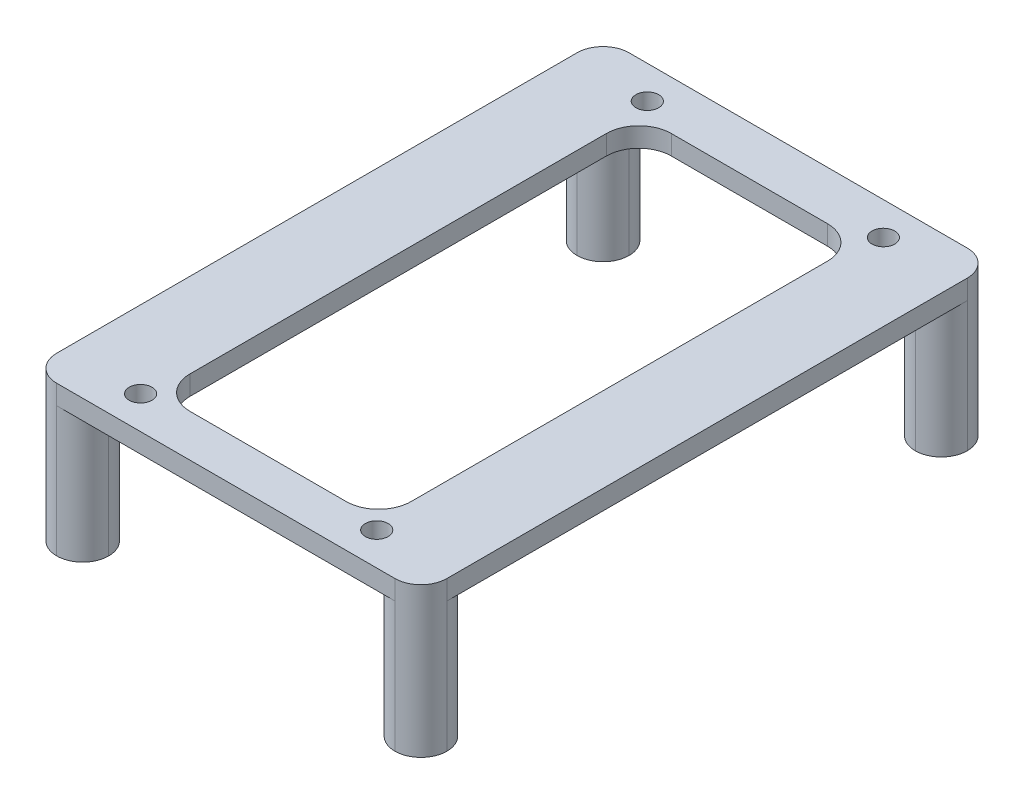
SolidWorks part; units mm, degrees
ref_plane "Front Plane" through (0, 0, 0) normal (0, 0, 1) x (1, 0, 0)
ref_plane "Top Plane" through (0, 0, 0) normal (0, 1, 0) x (1, 0, 0)
ref_plane "Right Plane" through (0, 0, 0) normal (1, 0, 0) x (0, 0, -1)
sketch "Sketch1" plane through (0, 0, 0) normal (0, 1, 0) x (1, 0, 0)
  line L0 (11.85, 82.95) -> (0, 88) construction
  line L1 (0, 0) -> (60, 0)
  line L2 (0, 0) -> (0, 88)
  line L3 (0, 88) -> (60, 88)
  line L4 (60, 0) -> (60, 88)
  line L5 (11.85, 82.95) -> (48.15, 82.95) construction
  line L6 (11.85, 82.95) -> (11.85, 5.05) construction
  line L7 (11.85, 5.05) -> (48.15, 5.05) construction
  line L8 (48.15, 82.95) -> (48.15, 5.05) construction
  line L9 (48.15, 82.95) -> (60, 88) construction
  line L10 (0, 0) -> (11.85, 5.05) construction
  line L11 (48.15, 5.05) -> (60, 0) construction
  line L13 (13, 80.5) -> (47, 80.5)
  line L14 (13, 80.5) -> (13, 6.5)
  line L15 (13, 6.5) -> (47, 6.5)
  line L16 (47, 80.5) -> (47, 6.5)
  circle A0 centre (11.85, 82.95) radius 1.75
  circle A1 centre (48.15, 82.95) radius 1.75
  circle A2 centre (48.15, 5.05) radius 1.75
  circle A3 centre (11.85, 5.05) radius 1.75
  point P18 (11.85, 81.2068)
  point P19 (10.1, 83.2938)
  dimension "D5" = 3.5
  dimension "D1" = 60
  dimension "D2" = 88
  dimension "D3" = 77.9
  dimension "D4" = 36.3
  dimension "D6" = 34
  dimension "D7" = 74
  dimension "D8" = 7.5
  dimension "D9" = 13
extrude "Boss-Extrude1" add sketch "Sketch1" along normal blind 3
fillet "Fillet1" radius 5 4 edges at (47, 1.5, -80.5) (47, 1.5, -6.5) (13, 1.5, -6.5) (13, 1.5, -80.5)
sketch "Sketch2" plane through (0, 0, 0) normal (0, -1, 0) x (1, 0, 0)
  line L0 (60, 0) -> (60, -88) construction
  line L1 (0, 0) -> (8, 0)
  line L2 (0, 0) -> (0, -8)
  line L3 (0, -8) -> (8, -8)
  line L4 (8, 0) -> (8, -8)
  line L5 (60, 0) -> (52, 0)
  line L6 (60, 0) -> (60, -8)
  line L7 (60, -8) -> (52, -8)
  line L8 (52, 0) -> (52, -8)
  line L9 (0, 0) -> (60, 0) construction
  line L10 (0, -88) -> (8, -88)
  line L11 (0, -88) -> (0, -80)
  line L12 (0, -80) -> (8, -80)
  line L13 (8, -88) -> (8, -80)
  line L14 (60, -88) -> (52, -88)
  line L15 (60, -88) -> (60, -80)
  line L16 (60, -80) -> (52, -80)
  line L17 (52, -88) -> (52, -80)
  point P23 (8.1501, -14.5717)
  dimension "D1" = 8
  dimension "D2" = 8
extrude "Boss-Extrude2" add sketch "Sketch2" along normal blind 20
fillet "Fillet2" radius 4 16 edges at (60, -10, -8) (8, -10, -8) (8, -10, 0) (0, -10, -8) (52, -10, 0) (52, -10, -8) (52, -10, -88) (60, -10, -80) (52, -10, -80) (8, -10, -88) (0, -10, -80) (8, -10, -80) (0, -8.5, -88) (60, -8.5, -88) (60, -8.5, 0) (0, -8.5, 0)
sketch "Sketch3" plane through (0, -20, 0) normal (0, -1, 0) x (1, 0, 0)
  circle A0 centre (4, -4) radius 2.6
  circle A1 centre (56, -4) radius 2.6
  circle A2 centre (56, -84) radius 2.6
  circle A3 centre (4, -84) radius 2.6
  dimension "D1" = 5.2
extrude "Cut-Extrude1" cut sketch "Sketch3" against normal blind 4
